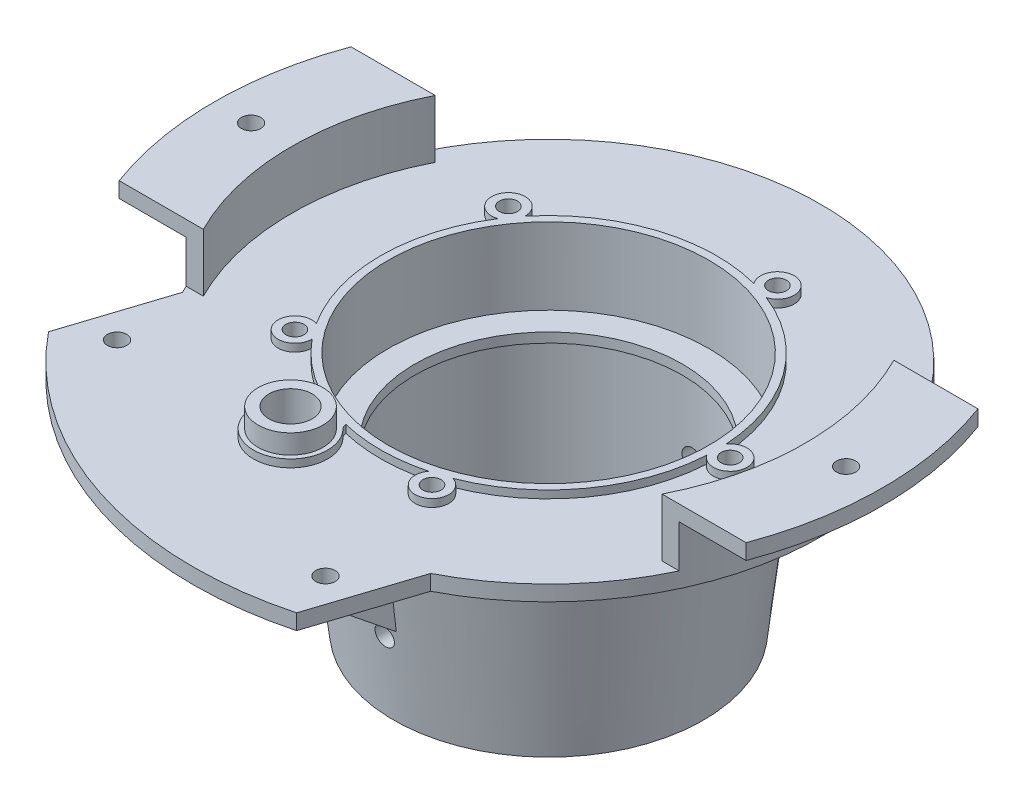
SolidWorks part; units mm, degrees
ref_plane "Front Plane" through (0, 0, 0) normal (0, 0, 1) x (1, 0, 0)
ref_plane "Top Plane" through (0, 0, 0) normal (0, 1, 0) x (1, 0, 0)
ref_plane "Right Plane" through (0, 0, 0) normal (1, 0, 0) x (0, 0, -1)
sketch "Sketch1" plane through (0, 0, 0) normal (0, 0, 1) x (1, 0, 0)
  line L26 (-70.5, -4) -> (-70.5, 11)
  line L27 (-70.5, 11) -> (-86.5, 11)
  line L28 (-86.5, 11) -> (-86.5, 15)
  line L29 (-86.5, 15) -> (-66.5, 15)
  line L30 (-66.5, 15) -> (-66.5, 0)
  line L31 (-66.5, 0) -> (-41.5, 0)
  line L36 (-37.1, -20.3) -> (-37.1, -60.3)
  line L37 (-37.1, -60.3) -> (-40.1, -60.3)
  line L38 (-37.5, -17.8) -> (-34.6, -17.8)
  line L41 (-37.5, -17.8) -> (-41.5, -17.8)
  line L42 (-41.5, 0) -> (-41.5, -17.8)
  line L43 (-34.6, -17.8) -> (-34.6, -20.3)
  line L44 (-34.6, -20.3) -> (-37.1, -20.3)
  line L45 (-70.5, -4) -> (-56.5, -4)
  line L47 (-45.5, -15) -> (-40.1, -60.3)
  line L48 (-56.5, -4) -> (-45.5, -15)
  dimension "D2" = 4
  dimension "D3" = 2.5
  dimension "D4" = 41.5
  dimension "D5" = 17.8
  dimension "D6" = 2.5
  dimension "D7" = 15
  dimension "D8" = 4
  dimension "D9" = 37.1
  dimension "D10" = 3
  dimension "D11" = 20
  dimension "D12" = 4
  dimension "D13" = 4
  dimension "D14" = 40
  dimension "D15" = 4
  dimension "D16" = 25
  dimension "D17" = 15
  dimension "D18" = 15
ref_axis "Axis1" through (0, -100.5, 0) along (0, 1, 0)
revolve "Revolve1" add sketch "Sketch1" angle 360 about axis through (0, -100.5, 0) along (0, 1, 0)
sketch "Sketch2" plane through (0, 11, 0) normal (0, -1, 0) x (1, 0, 0)
  circle A0 centre (77, 0) radius 2.5
  circle A1 centre (-77, 0) radius 2.5
  dimension "D1" = 5
  dimension "D3" = 77
  dimension "D2" = 77
extrude "Cut-Extrude3" cut sketch "Sketch2" against normal up to surface (4 mm away) up to face at (0, 15, -86.5)
sketch "Sketch3" plane through (0, 15, 0) normal (0, 1, 0) x (1, 0, 0)
  line L0 (-59.3485, -30) -> (-81.1311, -30)
  line L1 (81.1311, -30) -> (59.3485, -30)
  line L5 (81.1311, 30) -> (59.3485, 30)
  line L9 (-59.3485, 30) -> (-81.1311, 30)
  circle A0 centre (0, 0) radius 86.5 construction
  circle A1 centre (-77, 0) radius 2.5 construction
  arc A2 (-81.1311, -30) -> (81.1311, -30) centre (0, 0) ccw
  circle A3 centre (0, 0) radius 66.5 construction
  arc A4 (-59.3485, -30) -> (59.3485, -30) centre (0, 0) ccw
  arc A5 (59.3485, 30) -> (-59.3485, 30) centre (0, 0) ccw
  arc A6 (81.1311, 30) -> (-81.1311, 30) centre (0, 0) ccw
  dimension "D2" = 30
  dimension "D1" = 30
extrude "Cut-Extrude4" cut sketch "Sketch3" against normal up to surface (15 mm away) up to face at (0, 0, -66.5)
sketch "Sketch6" plane through (0, 0, 0) normal (0, 0, 1) x (1, 0, 0)
  line L0 (0, -100.5) -> (0, 20.5) construction
  line L2 (-40.1, -60.3) -> (40.1, -60.3) construction
  circle A0 centre (0, -40.3) radius 2.5
  dimension "D1" = 5
  dimension "D2" = 20
extrude "Cut-Extrude6" cut sketch "Sketch6" against normal through all both and the other way through all
sketch "Sketch7" plane through (0, 0, 0) normal (0, 1, 0) x (1, 0, 0)
  circle A0 centre (47, 0) radius 2.35
  dimension "D1" = 4.7
  dimension "D2" = 47
extrude "Cut-Extrude7" cut sketch "Sketch7" against normal up to surface (13.4413 mm away) contours A0 up to face at (0, -15, -45.5)
pattern_circular "CirPattern1" count 5 every 72 about axis through (0, -100.5, 0) along (0, 1, 0) of "Cut-Extrude7"
sketch "Sketch9" plane through (0, 0, 0) normal (0, 1, 0) x (1, 0, 0)
  circle A0 centre (-16.377, -50.4063) radius 5.6
  circle A3 centre (-38.0238, -27.6259) radius 2.35 construction
  circle A4 centre (14.5238, -44.6997) radius 2.35 construction
  dimension "D1" = 11.2
  dimension "D3" = 31.425
  dimension "D2" = 53
  dimension "D4" = 31.4233
extrude "Cut-Extrude8" cut sketch "Sketch9" against normal through all contours A0
sketch "Sketch8" plane through (0, 0, 0) normal (0, 1, 0) x (1, 0, 0)
  circle A0 centre (0, 0) radius 41.5 construction
  circle A1 centre (0, 0) radius 41.5
  arc A2 (-33.6747, -27.5366) -> (-17.3102, -39.9075) centre (0, 0) ccw
  circle A3 centre (-38.0238, -27.6259) radius 2.35 construction
  circle A4 centre (14.5238, -44.6997) radius 2.35 construction
  circle A5 centre (47, 0) radius 2.35 construction
  circle A6 centre (14.5238, 44.6997) radius 2.35 construction
  circle A7 centre (-38.0238, 27.6259) radius 2.35 construction
  circle A8 centre (-38.0238, -27.6259) radius 2.35
  circle A9 centre (14.5238, -44.6997) radius 2.35
  circle A10 centre (47, 0) radius 2.35
  circle A11 centre (14.5238, 44.6997) radius 2.35
  circle A12 centre (-38.0238, 27.6259) radius 2.35
  arc A13 (-33.6747, 27.5366) -> (-36.5949, 23.5173) centre (-38.0238, 27.6259) ccw
  arc A14 (15.7828, 40.5358) -> (11.0578, 42.0711) centre (14.5238, 44.6997) ccw
  arc A15 (43.429, -2.4841) -> (43.429, 2.4841) centre (47, 0) ccw
  arc A16 (11.0578, -42.0711) -> (15.7828, -40.5358) centre (14.5238, -44.6997) ccw
  arc A17 (-36.5949, -23.5173) -> (-33.6747, -27.5366) centre (-38.0238, -27.6259) ccw
  arc A18 (15.7828, -40.5358) -> (43.429, -2.4841) centre (0, 0) ccw
  circle A19 centre (-38.0238, -27.6259) radius 4.35 construction
  circle A20 centre (0, 0) radius 43.5 construction
  circle A21 centre (14.5238, -44.6997) radius 4.35 construction
  arc A22 (43.429, 2.4841) -> (15.7828, 40.5358) centre (0, 0) ccw
  arc A23 (11.0578, 42.0711) -> (-33.6747, 27.5366) centre (0, 0) ccw
  circle A24 centre (47, 0) radius 4.35 construction
  arc A25 (-36.5949, 23.5173) -> (-36.5949, -23.5173) centre (0, 0) ccw
  circle A26 centre (14.5238, 44.6997) radius 4.35 construction
  circle A27 centre (-38.0238, 27.6259) radius 4.35 construction
  circle A28 centre (-16.377, -50.4063) radius 5.6 construction
  circle A29 centre (-16.377, -50.4063) radius 5.6
  arc A30 (-19.3485, -41.2778) -> (-9.394, -43.8186) centre (-16.377, -50.4063) ccw
  arc A31 (-17.3102, -39.9075) -> (-19.3485, -41.2778) centre (-19.5582, -38.7645) cw
  arc A32 (-10.1543, -42.2982) -> (-9.394, -43.8186) centre (-8.0531, -42.1977) ccw
  arc A33 (-10.1543, -42.2982) -> (11.0578, -42.0711) centre (0, 0) ccw
  circle A34 centre (-16.377, -50.4063) radius 9.6 construction
  point P4 (18.6238, -44.6997)
  point P23 (-33.9238, 27.6259)
  point P29 (41.5993, 12.7182)
  point P30 (-33.9238, -27.6259)
  point P39 (51.1, 0)
  point P42 (18.6238, 44.6997)
  point P57 (-8.777, -50.4063)
  dimension "D1" = 2
  dimension "D2" = 2
  dimension "D3" = 4
extrude "Boss-Extrude1" add sketch "Sketch8" along normal blind 2
sketch "Sketch10" plane through (0, 2, 0) normal (0, 1, 0) x (1, 0, 0)
  circle A0 centre (-16.377, -50.4063) radius 5.6 construction
  circle A1 centre (-16.377, -50.4063) radius 5.6
  circle A2 centre (-16.377, -50.4063) radius 8.4
  dimension "D1" = 2.8
extrude "Boss-Extrude2" add sketch "Sketch10" along normal blind 5
ref_point "Point1"
sketch "Sketch15" plane through (0, 0, 0) normal (0, 1, 0) x (1, 0, 0)
  line L0 (0, 0) -> (-16.377, -50.4063)
  line L1 (-16.377, -50.4063) -> (-33.367, -102.6994)
sketch "Sketch11" plane through (0, 0, 0) normal (0, 1, 0) x (1, 0, 0)
  line L0 (-62.9109, -31.8193) -> (-71.4162, -57.9976)
  line L1 (32.1953, -62.7193) -> (23.69, -88.8976)
  line L3 (-16.377, -50.4063) -> (-33.367, -102.6994) construction
  arc A0 (-63.7985, -30) -> (63.7985, -30) centre (0, 0) ccw construction
  arc A1 (-62.9109, -31.8193) -> (32.1953, -62.7193) centre (0, 0) ccw
  arc A4 (23.69, -88.8976) -> (-71.4162, -57.9976) centre (0, 0) cw
  point P3 (0, 0)
  point P4 (-86.4221, -40.6383)
  point P5 (86.4221, -40.6383)
  point P11 (-21.7845, -67.0499)
  point P14 (-28.428, -87.4977)
  dimension "D2" = 21.5
  dimension "D1" = 100
extrude "Boss-Extrude3" add sketch "Sketch11" against normal up to surface (4 mm away) up to face at (-0.3244, -4, 0.9986)
ref_axis "Axis2" through (23.69, 0, 88.8976) along (-0.9511, 0, -0.309)
sketch "Sketch16" plane through (0, 0, 0) normal (0, 1, 0) x (1, 0, 0)
  line L0 (23.69, -88.8976) -> (32.1953, -62.7193) construction
  line L1 (-62.9109, -31.8193) -> (-71.4162, -57.9976) construction
  line L2 (23.69, -88.8976) -> (-71.4162, -57.9976) construction
  circle A0 centre (19.1715, -76.915) radius 2.5
  circle A1 centre (-60.7177, -50.959) radius 2.5
  dimension "D3" = 5
  dimension "D4" = 10
  dimension "D5" = 10
  dimension "D1" = 8
  dimension "D2" = 8
extrude "Cut-Extrude9" cut sketch "Sketch16" against normal up to surface (4 mm away)
sketch "Sketch17" plane through (0, 0, 0) normal (0, 1, 0) x (1, 0, 0)
  line L0 (0, 0) -> (-55.406, -73.4451)
  line L1 (0, 0) -> (1.6578, -91.9851)
  line L2 (-55.406, -73.4451) -> (1.6578, -91.9851)
  line L3 (0, 0) -> (-16.377, -50.4063)
  line L4 (-16.377, -50.4063) -> (-33.0404, -101.6941)
  arc A0 (-71.4162, -57.9976) -> (23.69, -88.8976) centre (0, 0) ccw construction
  point P10 (-26.8741, -82.7151)
  dimension "D1" = 60
ref_plane "Plane2" through (0, 0, 0) normal (-0.7983, 0, -0.6022) x (-0.6022, 0, 0.7983)
ref_plane "Plane3" through (0, 0, 0) normal (-0.9998, 0, 0.018) x (0.018, 0, 0.9998)
sketch "Sketch18" plane through (0, 0, 0) normal (-0.7983, 0, -0.6022) x (-0.6022, 0, 0.7983)
  line L2 (89.31, -4) -> (63.2893, -4) construction
  line L27 (27.5163, -15) -> (45.5, -15) construction
  line L29 (44.8194, -15) -> (42.0003, -38.1306)
  line L30 (42.0003, -38.1306) -> (84.2847, -4)
  line L31 (44.8194, -15) -> (55.4437, -4)
  line L32 (-56.5, -4) -> (56.5, -4) construction
  line L33 (55.4437, -4) -> (84.2847, -4)
extrude "Boss-Extrude8" add sketch "Sketch18" along normal mid plane 5
ref_plane "Plane4" through (0, 0, 0) normal (0.9511, 0, 0.309) x (0.309, 0, -0.9511)
mirror "Mirror1" about plane through (0, 0, 0) normal (0.9511, 0, 0.309) of "Boss-Extrude8"
